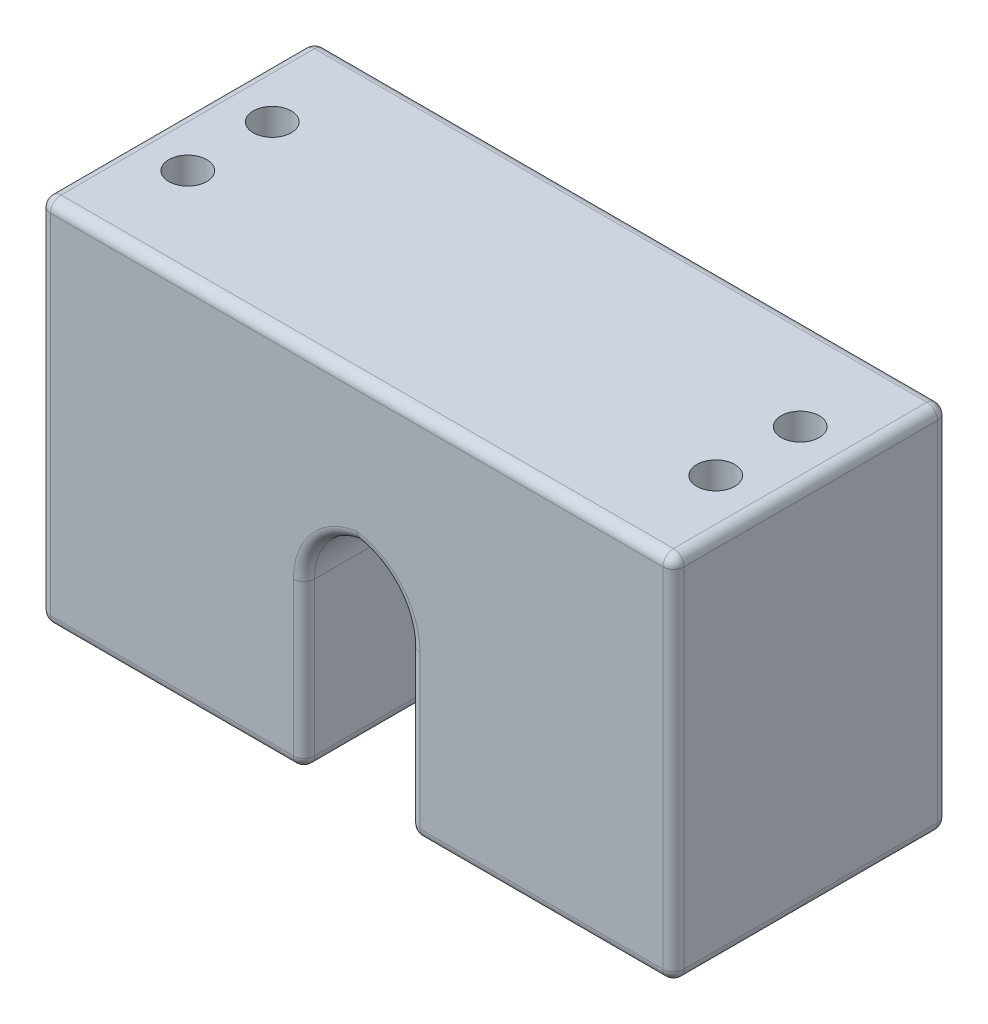
SolidWorks part; units mm, degrees
ref_plane "Piano frontale" through (0, 0, 0) normal (0, 0, 1) x (1, 0, 0)
ref_plane "Piano superiore" through (0, 0, 0) normal (0, 1, 0) x (1, 0, 0)
ref_plane "Piano destro" through (0, 0, 0) normal (1, 0, 0) x (0, 0, -1)
sketch "Schizzo1" plane through (0, -48.032, 0) normal (0, -1, 0) x (1, 0, 0)
  line L0 (-235.2009, -117.8045) -> (-19.2009, -117.8045) construction
  line L1 (-157.2009, -91.8045) -> (-97.2009, -91.8045)
  line L2 (-157.2009, -91.8045) -> (-157.2009, -117.8045)
  line L3 (-157.2009, -117.8045) -> (-97.2009, -117.8045)
  line L4 (-97.2009, -91.8045) -> (-97.2009, -117.8045)
  line L5 (-157.2009, -91.8045) -> (-97.2009, -117.8045) construction
  line L6 (-157.2009, -117.8045) -> (-97.2009, -91.8045) construction
  line L7 (-19.2009, -91.8045) -> (-235.2009, -91.8045) construction
  line L8 (-127.2009, -41.6665) -> (-127.2009, 30.9335) construction
  point P0 (-127.2009, -104.8045)
  dimension "D1" = 60
extrude "Estrusione-Estrusione1" add sketch "Schizzo1" along normal blind 35
sketch "Schizzo4" plane through (0, 0, -91.8045) normal (0, 0, 1) x (1, 0, 0)
  line L1 (-132.2009, -83.032) -> (-122.2009, -83.032)
  line L2 (-132.2009, -83.032) -> (-132.2009, -61.532)
  line L3 (-132.2009, -61.532) -> (-122.2009, -61.532)
  line L4 (-122.2009, -83.032) -> (-122.2009, -61.532)
  line L5 (-132.2009, -83.032) -> (-122.2009, -61.532) construction
  line L6 (-132.2009, -61.532) -> (-122.2009, -83.032) construction
  line L7 (-127.2009, 12.7933) -> (-127.2009, 85.3933) construction
  line L8 (-97.2009, -83.032) -> (-157.2009, -83.032) construction
  point P0 (-127.2009, -72.282)
  point P9 (-127.2009, -61.532)
  dimension "D1" = 10
  dimension "D2" = 21.5
extrude "Taglio-Estrusione2" cut sketch "Schizzo4" against normal through all
sketch "Schizzo2" plane through (0, -83.032, 0) normal (0, -1, 0) x (1, 0, 0)
  line L0 (-157.2009, -104.8045) -> (-97.2009, -104.8045) construction
  line L1 (-157.2009, -91.8045) -> (-157.2009, -117.8045) construction
  line L2 (-97.2009, -117.8045) -> (-97.2009, -91.8045) construction
  line L3 (-97.2009, -117.8045) -> (-97.2009, -104.438)
  line L4 (-157.2009, -91.8045) -> (-97.2009, -91.8045)
  line L5 (-157.2009, -91.8045) -> (-157.2009, -105.1711)
  line L6 (-147.2009, -99.8045) -> (-107.2009, -99.8045)
  line L7 (-97.2009, -91.8045) -> (-97.2009, -105.1711)
  line L8 (-147.2009, -104.438) -> (-107.2009, -104.438)
  line L9 (-157.2009, -117.8045) -> (-157.2009, -104.438)
  line L10 (-157.2009, -117.8045) -> (-97.2009, -117.8045)
  line L11 (-147.2009, -99.8045) -> (-147.2009, -104.438)
  line L12 (-127.2009, -91.8045) -> (-127.2009, -117.8045) construction
  line L13 (-107.2009, -99.8045) -> (-107.2009, -104.438)
  line L14 (-157.2009, -105.1711) -> (-157.2009, -104.438)
  line L15 (-97.2009, -105.1711) -> (-97.2009, -104.438)
  dimension "D1" = 5
  dimension "D2" = 10
extrude "Taglio-Estrusione1" cut sketch "Schizzo2" against normal offset from surface (30 mm away) 5 rebuild error yes up to face at (-127.2009, -48.032, -104.8045)
fillet "Raccordo1" radius 6 2 edges at (-122.2009, -61.532, -104.8045) (-132.2009, -61.532, -104.8045)
fillet "Raccordo3" radius 4 rebuild error yes
fillet "Raccordo2" radius 1 24 edges at (-127.2009, -48.032, -91.8045) (-127.2009, -48.032, -117.8045) (-157.2009, -65.532, -117.8045) (-157.2009, -48.032, -104.8045) (-157.2009, -65.532, -91.8045) (-97.2009, -65.532, -91.8045) (-97.2009, -48.032, -104.8045) (-97.2009, -65.532, -117.8045) (-97.2009, -83.032, -104.8045) (-122.2009, -83.032, -104.8045) (-132.2009, -83.032, -104.8045) (-157.2009, -83.032, -104.8045) (-122.2009, -75.282, -91.8045) (-123.6184, -63.659, -91.8045) (-130.7835, -63.659, -91.8045) (-132.2009, -75.282, -91.8045) (-132.2009, -75.282, -117.8045) (-130.7835, -63.659, -117.8045) (-123.6184, -63.659, -117.8045) (-122.2009, -75.282, -117.8045) (-109.7009, -83.032, -91.8045) (-109.7009, -83.032, -117.8045) (-144.7009, -83.032, -117.8045) (-144.7009, -83.032, -91.8045)
hole_wizard "Foro per Vite M3-1" positions "Schizzo5" profile "Schizzo6" hole size "M3" standard "ISO"
sketch "Schizzo5" plane through (0, -48.032, 0) normal (0, 1, 0) x (1, 0, 0)
  point P0 (-152.2009, 108.8045)
  point P3 (-102.2009, 108.8045)
  point P6 (-102.2009, 100.8045)
  point P9 (-152.2009, 100.8045)
sketch "Schizzo6" plane through (-152.2009, -48.032, -108.8045) normal (1, 0, 0) x (0, 0, 1)
  line L0 (0, 0) -> (0, 11.0815)
  line L1 (0, 11.0815) -> (1.8, 10)
  line L2 (1.8, 10) -> (1.8, 0)
  line L5 (1.8, 0) -> (0, 0)
  line L10 (0, 11.0815) -> (-1.8, 10) construction
  line L11 (0, -6.35) -> (0, 107.95) construction
  dimension "Hole Dia." = 3.6
  dimension "Hole Depth" = 10
  dimension "Drill Angle" = 118
sketch "Schizzo7" plane through (0, -53.032, 0) normal (0, -1, 0) x (1, 0, 0)
  line L1 (-148.7368, -108.8045) -> (-150.4689, -105.8045)
  line L2 (-150.4689, -105.8045) -> (-153.933, -105.8045)
  line L3 (-153.933, -105.8045) -> (-155.665, -108.8045)
  line L4 (-155.665, -108.8045) -> (-153.933, -111.8045)
  line L5 (-153.933, -111.8045) -> (-150.4689, -111.8045)
  line L6 (-150.4689, -111.8045) -> (-148.7368, -108.8045)
  line L7 (-153.933, -103.8045) -> (-150.4689, -103.8045)
  line L8 (-150.4689, -103.8045) -> (-148.7368, -100.8045)
  line L9 (-148.7368, -100.8045) -> (-150.4689, -97.8045)
  line L10 (-150.4689, -97.8045) -> (-153.933, -97.8045)
  line L11 (-153.933, -97.8045) -> (-155.665, -100.8045)
  line L12 (-155.665, -100.8045) -> (-153.933, -103.8045)
  line L13 (-100.4689, -103.8045) -> (-98.7368, -100.8045)
  line L14 (-98.7368, -100.8045) -> (-100.4689, -97.8045)
  line L15 (-100.4689, -97.8045) -> (-103.933, -97.8045)
  line L16 (-103.933, -97.8045) -> (-105.665, -100.8045)
  line L17 (-105.665, -100.8045) -> (-103.933, -103.8045)
  line L18 (-103.933, -103.8045) -> (-100.4689, -103.8045)
  line L19 (-100.4689, -111.8045) -> (-98.7368, -108.8045)
  line L20 (-98.7368, -108.8045) -> (-100.4689, -105.8045)
  line L21 (-100.4689, -105.8045) -> (-103.933, -105.8045)
  line L22 (-103.933, -105.8045) -> (-105.665, -108.8045)
  line L23 (-105.665, -108.8045) -> (-103.933, -111.8045)
  line L24 (-103.933, -111.8045) -> (-100.4689, -111.8045)
  circle A0 centre (-152.2009, -108.8045) radius 3 construction
  circle A1 centre (-152.2009, -100.8045) radius 3 construction
  circle A2 centre (-102.2009, -100.8045) radius 3 construction
  circle A3 centre (-102.2009, -108.8045) radius 3 construction
  dimension "D1" = 6
  dimension "D2" = 6
  dimension "D3" = 6
  dimension "D4" = 6
extrude "Taglio-Estrusione4" cut sketch "Schizzo7" along normal blind 6 and the other way blind 2
ref_plane "destro" through (-127.2009, 49.0933, -5.3665) normal (1, 0, 0) x (0, 0, -1)
ref_plane "superiore" through (0, 0, -150) normal (0, 0, 1) x (1, 0, 0)
equation "\"L\"=21.5"
equation "\"D2@Schizzo4\"=\"L\""
equation "\"D2@Schizzo7\"=\"D1@Schizzo7\""
equation "\"D3@Schizzo7\"=\"D1@Schizzo7\""
equation "\"D4@Schizzo7\"=\"D1@Schizzo7\""
